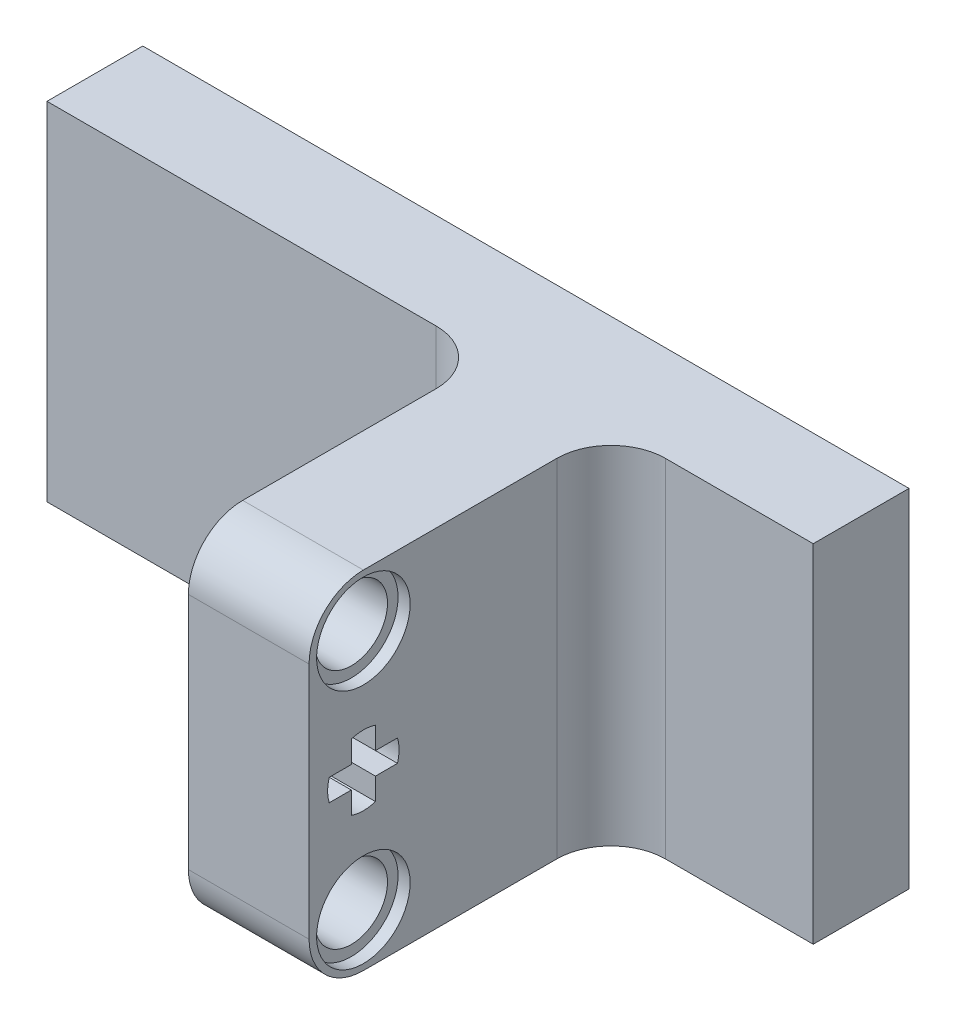
SolidWorks part; units mm, degrees
ref_plane "Front Plane" through (0, 0, 0) normal (0, 0, 1) x (1, 0, 0)
ref_plane "Top Plane" through (0, 0, 0) normal (0, 1, 0) x (1, 0, 0)
ref_plane "Right Plane" through (0, 0, 0) normal (1, 0, 0) x (0, 0, -1)
sketch "Sketch2" plane through (0, 0, 0) normal (0, 1, 0) x (1, 0, 0)
  line L0 (4, -3.175) -> (4, -19.6)
  line L1 (-25.4, 3.175) -> (25.4, 3.175)
  line L2 (-25.4, 3.175) -> (-25.4, -3.175)
  line L3 (-25.4, -3.175) -> (4, -3.175)
  line L4 (25.4, 3.175) -> (25.4, -3.175)
  line L5 (-25.4, 3.175) -> (25.4, -3.175) construction
  line L6 (-25.4, -3.175) -> (25.4, 3.175) construction
  line L8 (12, -19.6) -> (12, -3.175)
  line L9 (12, -3.175) -> (25.4, -3.175)
  line L10 (4, -19.6) -> (4, -23.2)
  line L11 (4, -23.2) -> (12, -23.2)
  line L12 (12, -23.2) -> (12, -19.6)
  point P0 (0, 0)
  dimension "D1" = 50.8
  dimension "D2" = 22.775
  dimension "D3" = 8
  dimension "D4" = 3.6
  dimension "D5" = 6.35
  dimension "D6" = 21.4
extrude "Boss-Extrude1" add sketch "Sketch2" along normal mid plane 23
sketch "Sketch3" plane through (12, 0, 0) normal (1, 0, 0) x (0, 0, -1)
  line L0 (-20.4, 0.7314) -> (-20.4, 2.1941)
  line L1 (-18.8, 2.1941) -> (-18.8, 0.7314)
  line L2 (-20.4, 0.7314) -> (-18.8, 0.7314) construction
  line L3 (-20.4, 0.7314) -> (-20.4, -0.7314) construction
  line L4 (-20.4, 0.7314) -> (-21.8627, 0.7314)
  line L5 (-21.8627, -0.7314) -> (-20.4, -0.7314)
  line L6 (-20.4, -0.7314) -> (-20.4, -2.1941)
  line L7 (-18.8, -2.1941) -> (-18.8, -0.7314)
  line L8 (-18.8, -0.7314) -> (-17.3373, -0.7314)
  line L9 (-18.8, 0.7314) -> (-17.3373, 0.7314)
  line L10 (-17.3373, 0.7314) -> (-15.4007, 0.7314)
  line L11 (-23.2, 11.5) -> (-23.2, -11.5) construction
  circle A0 centre (-19.6, 0) radius 2.5157 construction
  circle A1 centre (-19.6, 8) radius 3.1
  circle A2 centre (-19.6, -8) radius 3.1
  circle A3 centre (-19.6, 8) radius 2.4
  circle A4 centre (-19.6, -8) radius 2.4
  arc A5 (-20.4, 2.1941) -> (-18.8, 2.1941) centre (-19.6, -0.2798) cw
  arc A6 (-21.8627, 0.7314) -> (-21.8627, -0.7314) centre (-19.3677, 0) ccw
  arc A7 (-20.4, -2.1941) -> (-18.8, -2.1941) centre (-19.6, 0.2798) ccw
  arc A8 (-17.3373, 0.7314) -> (-17.3373, -0.7314) centre (-19.8323, 0) cw
  point P12 (-19.6, 0.7314)
  point P26 (-21.9677, 0)
  point P27 (-19.6, -2.3202)
  dimension "D1" = 6.2
  dimension "D2" = 4.8
  dimension "D7" = 2.6
  dimension "D3" = 8
  dimension "D4" = 8
  dimension "D5" = 1.4627
  dimension "D6" = 1.6
  dimension "D8" = 3.6
extrude "Cut-Extrude1" cut sketch "Sketch3" against normal through all contours A3 | A8 L9 L1 A5 L0 L4 A6 L5 L6 A7 L7 L8 | A4 region at (12, 0, 19.6) region at (12, 8, 19.6) region at (12, -8, 19.6)
extrude "Cut-Extrude2" cut sketch "Sketch3<3>" against normal blind 0.8 contours A1 A3 | A2 A4 region at (12, 8, 22.6123) region at (12, -8, 22.6123)
sketch "Sketch3<3>" plane through (12, 0, 0) normal (1, 0, 0) x (0, 0, -1) same geometry as "Sketch3"
ref_plane "Plane1" through (8, 0, 0) normal (1, 0, 0) x (0, 0, -1)
mirror "Mirror1" about plane through (8, 0, 0) normal (1, 0, 0) of "Cut-Extrude2"
fillet "Fillet1" radius 3.6 4 edges at (8, -11.5, 23.2) (8, 11.5, 23.2) (4, 0, 3.175) (12, 0, 3.175)
